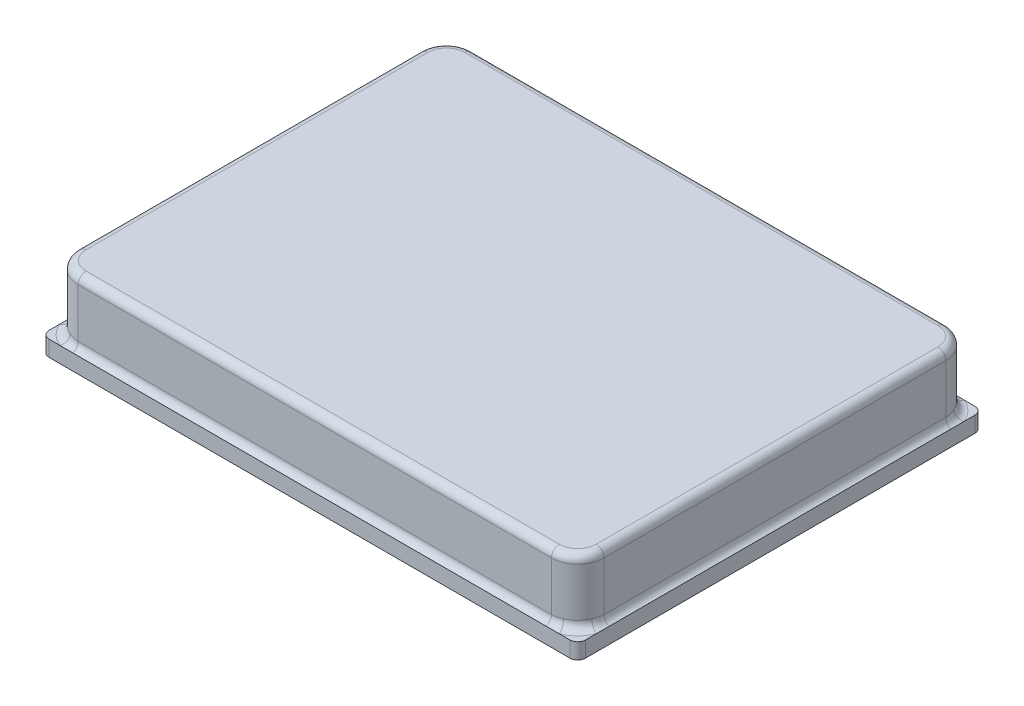
SolidWorks part; units mm, degrees
ref_plane "Front Plane" through (0, 0, 0) normal (0, 0, 1) x (1, 0, 0)
ref_plane "Top Plane" through (0, 0, 0) normal (0, 1, 0) x (1, 0, 0)
ref_plane "Right Plane" through (0, 0, 0) normal (1, 0, 0) x (0, 0, -1)
sketch "Sketch1" plane through (0, 0, 0) normal (0, 1, 0) x (1, 0, 0)
  line L0 (5.25, 5.25) -> (5.25, 144.75)
  line L1 (0, 0) -> (200, 0)
  line L2 (0, 0) -> (0, 150)
  line L3 (0, 150) -> (200, 150)
  line L4 (200, 0) -> (200, 150)
  line L5 (5.25, 144.75) -> (194.75, 144.75)
  line L6 (194.75, 5.25) -> (194.75, 144.75)
  line L7 (5.25, 5.25) -> (194.75, 5.25)
  line L8 (0, 150) -> (18.9, 131.1) construction
  line L9 (5.25, 144.75) -> (18.9, 144.75) construction
  line L10 (5.25, 144.75) -> (5.25, 131.1) construction
  line L11 (5.25, 131.1) -> (18.9, 131.1) construction
  line L12 (18.9, 144.75) -> (18.9, 131.1) construction
  line L13 (194.75, 144.75) -> (181.1, 144.75) construction
  line L14 (194.75, 144.75) -> (194.75, 131.1) construction
  line L15 (194.75, 131.1) -> (181.1, 131.1) construction
  line L16 (181.1, 144.75) -> (181.1, 131.1) construction
  line L17 (5.25, 5.25) -> (18.9, 5.25) construction
  line L18 (5.25, 5.25) -> (5.25, 18.9) construction
  line L19 (5.25, 18.9) -> (18.9, 18.9) construction
  line L20 (18.9, 5.25) -> (18.9, 18.9) construction
  line L21 (18.9, 144.75) -> (18.9, 140.1538)
  line L22 (100, 150) -> (100, 0) construction
  line L23 (9.8462, 131.1) -> (5.25, 131.1)
  line L24 (190.1538, 131.1) -> (194.75, 131.1)
  line L25 (200, 75) -> (0, 75) construction
  line L26 (181.1, 144.75) -> (181.1, 140.1538)
  line L27 (0, 0) -> (18.9, 18.9) construction
  line L28 (5.25, 18.9) -> (9.8462, 18.9)
  line L29 (18.9, 9.8462) -> (18.9, 5.25)
  line L30 (181.1, 9.8462) -> (181.1, 5.25)
  line L31 (194.75, 18.9) -> (190.1538, 18.9)
  circle A0 centre (9.8462, 140.1538) radius 6.5 construction
  circle A1 centre (9.8462, 140.1538) radius 3
  arc A2 (9.8462, 131.1) -> (18.9, 140.1538) centre (9.8462, 140.1538) ccw
  circle A3 centre (190.1538, 140.1538) radius 3
  arc A4 (190.1538, 131.1) -> (181.1, 140.1538) centre (190.1538, 140.1538) cw
  circle A5 centre (9.8462, 9.8462) radius 6.5 construction
  circle A6 centre (9.8462, 9.8462) radius 3
  arc A7 (18.9, 9.8462) -> (9.8462, 18.9) centre (9.8462, 9.8462) ccw
  arc A8 (181.1, 9.8462) -> (190.1538, 18.9) centre (190.1538, 9.8462) cw
  circle A9 centre (190.1538, 140.1538) radius 3
  circle A10 centre (190.1538, 9.8462) radius 3
  dimension "D6" = 13
  dimension "D7" = 6
  dimension "D8" = 13
  dimension "D1" = 150
  dimension "D2" = 200
  dimension "D4" = 162.2
  dimension "D5" = 112.2
  dimension "D3" = 5.25
extrude "Boss-Extrude1" add sketch "Sketch1" along normal blind 24.5 contours L1 L4 L3 L2 L7 L0 L5 L6 | L29 A7 L28 L0 L7 A6 | L23 A2 L21 L5 L0 A1 | A4 L24 L6 L5 L26 A3 | A8 L30 L7 L6 L31 A10 region at (5.443, 0, -12.075) region at (5.443, 0, -137.925) region at (181.293, 0, -7.5481) region at (187.925, 0, -144.557) region at (2.5, 0, -75)
sketch "Sketch2" plane through (0, 24.5, 0) normal (0, 1, 0) x (1, 0, 0)
  line L1 (0, 150) -> (200, 150)
  line L2 (0, 150) -> (0, 0)
  line L3 (0, 0) -> (200, 0)
  line L4 (200, 150) -> (200, 0)
extrude "Boss-Extrude2" add sketch "Sketch2" along normal blind 5
sketch "Sketch3" plane through (0, 0, 0) normal (0, -1, 0) x (1, 0, 0)
  line L14 (18.9, -5.25) -> (181.1, -5.25) construction
  line L15 (5.25, -5.25) -> (194.75, -5.25)
  line L16 (5.25, -5.25) -> (5.25, -144.75)
  line L17 (5.25, -144.75) -> (194.75, -144.75)
  line L18 (202, -152) -> (202, 2)
  line L19 (-2, -152) -> (202, -152)
  line L20 (-2, 2) -> (-2, -152)
  line L21 (202, 2) -> (-2, 2)
  line L22 (202, -152) -> (202, 2)
  line L23 (-2, -152) -> (202, -152)
  line L24 (-2, 2) -> (-2, -152)
  line L25 (202, 2) -> (-2, 2)
  line L26 (194.75, -5.25) -> (194.75, -144.75)
  line L27 (5.25, -18.9) -> (5.25, -131.1) construction
  line L28 (18.9, -144.75) -> (181.1, -144.75) construction
  line L29 (194.75, -18.9) -> (194.75, -131.1) construction
  dimension "D1" = 2
extrude "Boss-Extrude3" add sketch "Sketch3" against normal blind 5
sketch "Sketch4" plane through (0, 0, 0) normal (0, -1, 0) x (1, 0, 0)
  line L0 (0, 0) -> (0, -150)
  line L1 (-2, 2) -> (202, 2)
  line L2 (-2, 2) -> (-2, -152)
  line L3 (-2, -152) -> (202, -152)
  line L4 (202, 2) -> (202, -152)
  line L5 (0, -150) -> (200, -150)
  line L6 (200, 0) -> (200, -150)
  line L7 (0, 0) -> (200, 0)
  dimension "D1" = 2
extrude "Boss-Extrude4" add sketch "Sketch4" along normal blind 1
fillet "Fillet1" radius 10 4 edges at (200, 17.25, -150) (200, 17.25, 0) (0, 17.25, -150) (0, 17.25, 0)
fillet "Fillet2" radius 3 15 edges at (197.0711, 5, -2.9289) (197.0711, 5, -147.0711) (2.9289, 5, -147.0711) (197.0711, 29.5, -2.9289) (100, 29.5, 0) (2.9289, 29.5, -2.9289) (0, 29.5, -75) (2.9289, 29.5, -147.0711) (100, 29.5, -150) (197.0711, 29.5, -147.0711) (200, 29.5, -75) (2.9289, 5, -2.9289) (-2, 2, 2) (202, 2, 2) (202, 2, -152)
